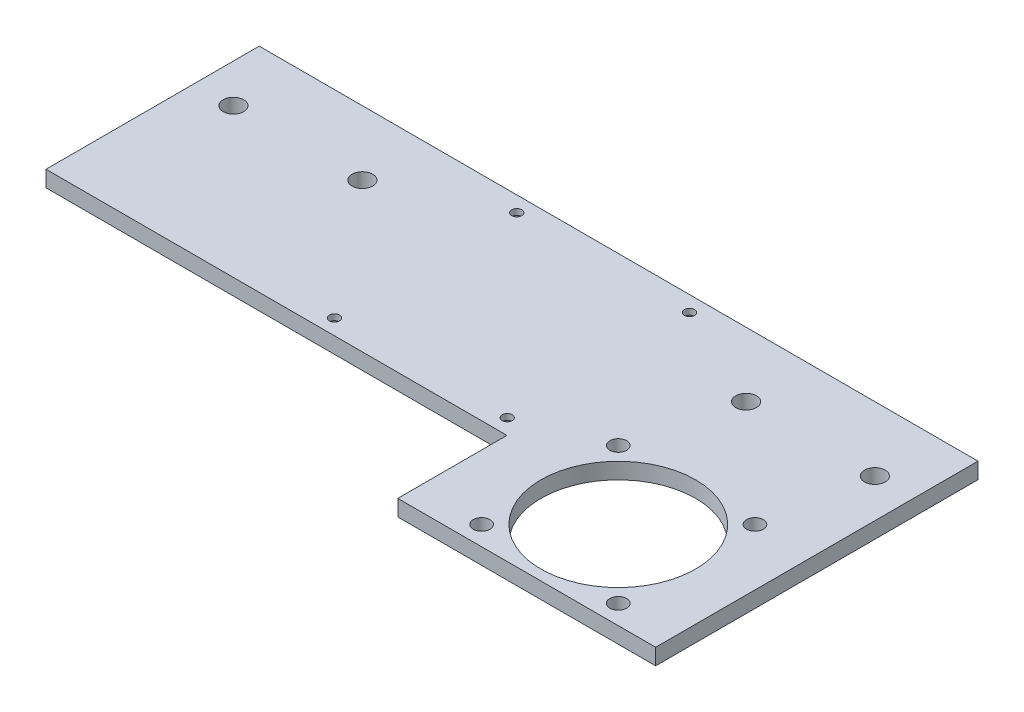
SolidWorks part; units mm, degrees
ref_plane "Front Plane" through (0, 0, 0) normal (0, 0, 1) x (1, 0, 0)
ref_plane "Top Plane" through (0, 0, 0) normal (0, 1, 0) x (1, 0, 0)
ref_plane "Right Plane" through (0, 0, 0) normal (1, 0, 0) x (0, 0, -1)
sketch "Sketch1" plane through (0, 0, 0) normal (0, 1, 0) x (1, 0, 0)
  line L1 (20, -21) -> (-20, -21)
  line L2 (20, -21) -> (20, 21)
  line L3 (20, 21) -> (-20, 21)
  line L4 (-20, -21) -> (-20, 21)
  line L5 (20, -21) -> (-20, 21) construction
  line L6 (20, 21) -> (-20, -21) construction
  point P0 (0, 0)
  dimension "D1" = 40
  dimension "D2" = 42
extrude "Boss-Extrude1" add sketch "Sketch1" along normal blind 3.175
sketch "Sketch2" plane through (0, 3.175, 0) normal (0, 1, 0) x (1, 0, 0)
  line L0 (20, -21) -> (20, 21) construction
  line L1 (-20, -21) -> (20, -21) construction
  line L2 (0, -21) -> (0, 21) construction
  line L3 (20, 21) -> (-20, 21) construction
  line L4 (20, 0) -> (-20, 0) construction
  line L5 (-20, 21) -> (-20, -21) construction
  line L6 (20, -21) -> (-20, -21) construction
  circle A0 centre (17.016, -17.952) radius 1
  circle A1 centre (-17.016, -17.952) radius 1
  circle A2 centre (17.016, 17.952) radius 1
  circle A3 centre (-17.016, 17.952) radius 1
  dimension "D1" = 2
  dimension "D2" = 17.016
  dimension "D3" = 3.048
extrude "Cut-Extrude1" cut sketch "Sketch2" against normal through all
sketch "Sketch3" plane through (0, 3.175, 0) normal (0, 1, 0) x (1, 0, 0)
  line L0 (20, 21) -> (-20, 21) construction
  line L1 (20, -42.5) -> (70.8, -42.5)
  line L2 (20, -42.5) -> (20, 21)
  line L3 (20, 21) -> (70.8, 21)
  line L4 (70.8, -42.5) -> (70.8, 21)
  line L5 (-20, 21) -> (-70.8, 21)
  line L6 (-20, 21) -> (-20, -42.5)
  line L7 (-20, -42.5) -> (-70.8, -42.5)
  line L8 (-70.8, 21) -> (-70.8, -42.5)
  line L10 (-20, -42.5) -> (-20, -67.9)
  line M17 (-20, 21) -> (-20, -21)
  line M18 (-20, -21) -> (20, -21)
  line M19 (20, -21) -> (20, 21)
  dimension "D1" = 50.8
  dimension "D2" = 50.8
  dimension "D4" = 63.5
extrude "Boss-Extrude2" add sketch "Sketch3" against normal blind 3.175 contours L1 L4 L3 M19 | L10 M18 | L5 L8 L7 M17 region at (45.4, 3.175, 10.75) region at (-45.4, 3.175, 10.75)
sketch "Sketch4" plane through (0, 3.175, 0) normal (0, 1, 0) x (1, 0, 0)
  line L0 (70.8, 21) -> (-70.8, 21) construction
  line L1 (70.8, -42.5) -> (70.8, 21) construction
  line L2 (-70.8, 21) -> (-70.8, -42.5) construction
  circle A0 centre (63.18, 8.3) radius 2.032
  circle A1 centre (37.8145, 8.3) radius 2.032
  circle A2 centre (-37.78, 8.3) radius 2.032
  circle A3 centre (-63.18, 8.3) radius 2.032
  dimension "D1" = 4.064
  dimension "D6" = 4.064
  dimension "D7" = 4.064
  dimension "D8" = 4.064
  dimension "D2" = 12.7
  dimension "D3" = 7.62
  dimension "D4" = 25.3655
  dimension "D5" = 25.4
  dimension "D9" = 7.62
extrude "Cut-Extrude2" cut sketch "Sketch4" against normal through all
sketch "Sketch7" plane through (0, 0, 0) normal (0, -1, 0) x (1, 0, 0)
  line L0 (0, 21) -> (0, -21) construction
  line L1 (-20, 21) -> (20, 21) construction
  line L2 (70.8, -21) -> (-70.8, -21) construction
  line L3 (-70.8, 0) -> (70.8, 0) construction
  line L4 (-70.8, -21) -> (-70.8, 42.5) construction
  line L5 (70.8, 42.5) -> (70.8, -21) construction
  circle A0 centre (-17.016, 17.952) radius 2.5
  circle A1 centre (17.016, 17.952) radius 2.5
  circle A2 centre (17.016, -17.952) radius 2.5
  circle A3 centre (-17.016, -17.952) radius 2.5
extrude "Cut-Extrude4" cut sketch "Sketch7" against normal blind 2
sketch "Sketch8" plane through (0, 0, 0) normal (0, -1, 0) x (-1, 0, 0)
  line L0 (-20, -42.5) -> (-70.8, -42.5) construction
  line L1 (-20, -42.5) -> (-20, -21) construction
  line L2 (-70.8, -42.5) -> (-70.8, 21) construction
  circle A0 centre (-32.7, -38.69) radius 1.651
  circle A1 centre (-32.7, -11.766) radius 1.651
  circle A2 centre (-59.624, -38.69) radius 1.651
  circle A3 centre (-59.624, -11.766) radius 1.651
  dimension "D1" = 3.302
  dimension "D2" = 3.302
  dimension "D4" = 3.302
  dimension "D12" = 3.302
  dimension "D3" = 26.924
  dimension "D5" = 26.924
  dimension "D6" = 26.924
  dimension "D7" = 26.924
  dimension "D8" = 3.81
  dimension "D9" = 12.7
  dimension "D10" = 12.7
  dimension "D11" = 11.176
extrude "Cut-Extrude5" cut sketch "Sketch8" against normal through all
sketch "Sketch9" plane through (0, 0, 0) normal (0, -1, 0) x (-1, 0, 0)
  line L0 (-32.7, -38.69) -> (-32.7, -11.766) construction
  line L1 (-32.7, -11.766) -> (-59.624, -11.766) construction
  line L2 (-59.624, -11.766) -> (-59.624, -38.69) construction
  line L3 (-59.624, -38.69) -> (-32.7, -38.69) construction
  line L4 (-46.162, -38.69) -> (-46.162, -11.766) construction
  line L5 (-32.7, -25.228) -> (-59.624, -25.228) construction
  line L6 (0, -21) -> (0, 21) construction
  line L7 (20, -21) -> (-20, -21) construction
  line L8 (-70.8, 21) -> (70.8, 21) construction
  circle A0 centre (-46.162, -25.228) radius 15.24
  dimension "D1" = 30.48
extrude "Cut-Extrude6" cut sketch "Sketch9" against normal through all
sketch "Sketch10" plane through (0, 3.175, 0) normal (0, 1, 0) x (1, 0, 0)
  line L1 (-20, -21) -> (-70.8, -21)
  line L2 (-20, -21) -> (-20, -42.5)
  line L3 (-20, -42.5) -> (-70.8, -42.5)
  line L4 (-70.8, -21) -> (-70.8, -42.5)
extrude "Cut-Extrude7" cut sketch "Sketch10" against normal through all both and the other way through all
